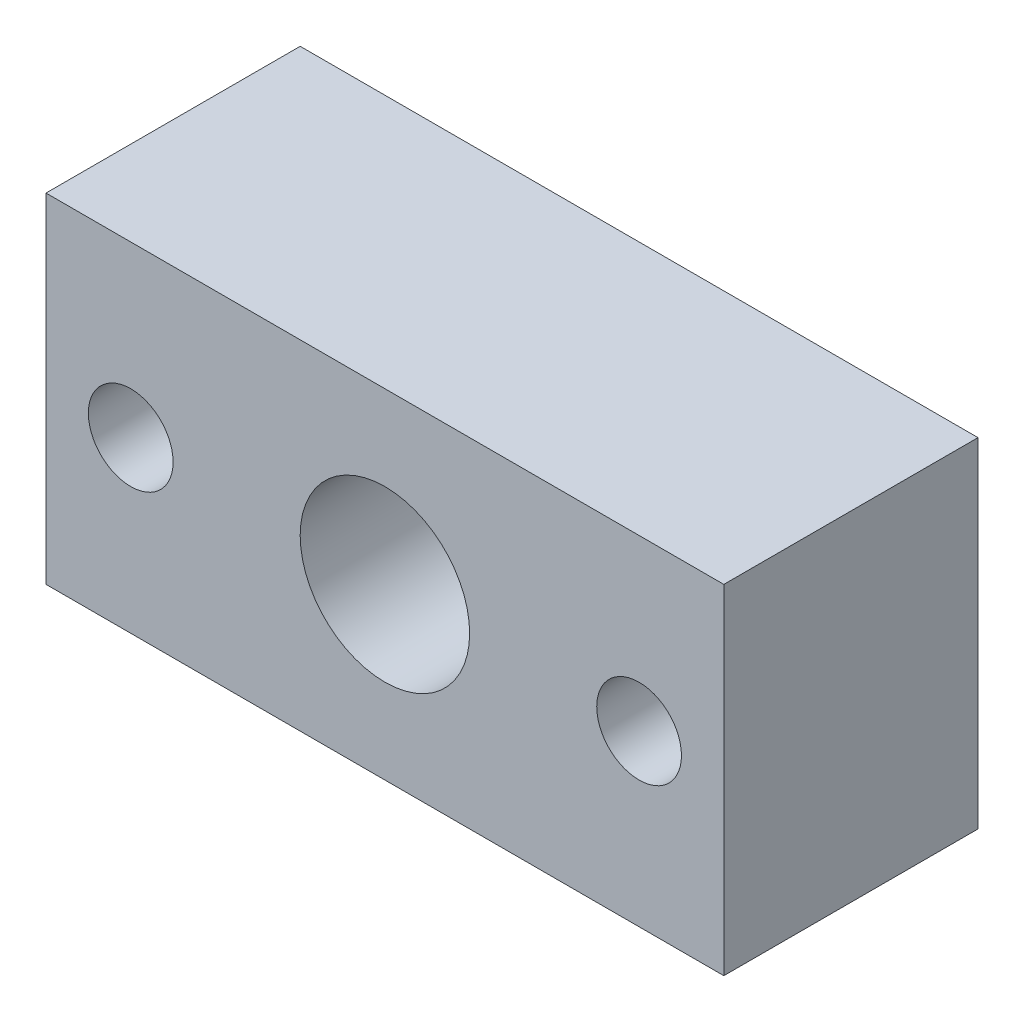
SolidWorks part; units mm, degrees
ref_plane "Front Plane" through (0, 0, 0) normal (0, 0, 1) x (1, 0, 0)
ref_plane "Top Plane" through (0, 0, 0) normal (0, 1, 0) x (1, 0, 0)
ref_plane "Right Plane" through (0, 0, 0) normal (1, 0, 0) x (0, 0, -1)
sketch "Sketch1" plane through (0, 0, 0) normal (0, 0, 1) x (1, 0, 0)
  line L1 (0, 0) -> (40, 0)
  line L2 (0, 0) -> (0, 20)
  line L3 (0, 20) -> (40, 20)
  line L4 (40, 0) -> (40, 20)
  circle A0 centre (20, 10) radius 5
  circle A1 centre (35, 10) radius 2.5
  circle A2 centre (5, 10) radius 2.5
  dimension "D1" = 40
  dimension "D2" = 20
extrude "Boss-Extrude1" add sketch "Sketch1" along normal blind 15
sketch "Sketch3" plane through (0, 0, 0) normal (0, 0, -1) x (-1, 0, 0)
  circle A0 centre (-5, 10) radius 4.15
  circle A1 centre (-35, 10) radius 4.15
extrude "Cut-Extrude1" cut sketch "Sketch3" against normal blind 5
